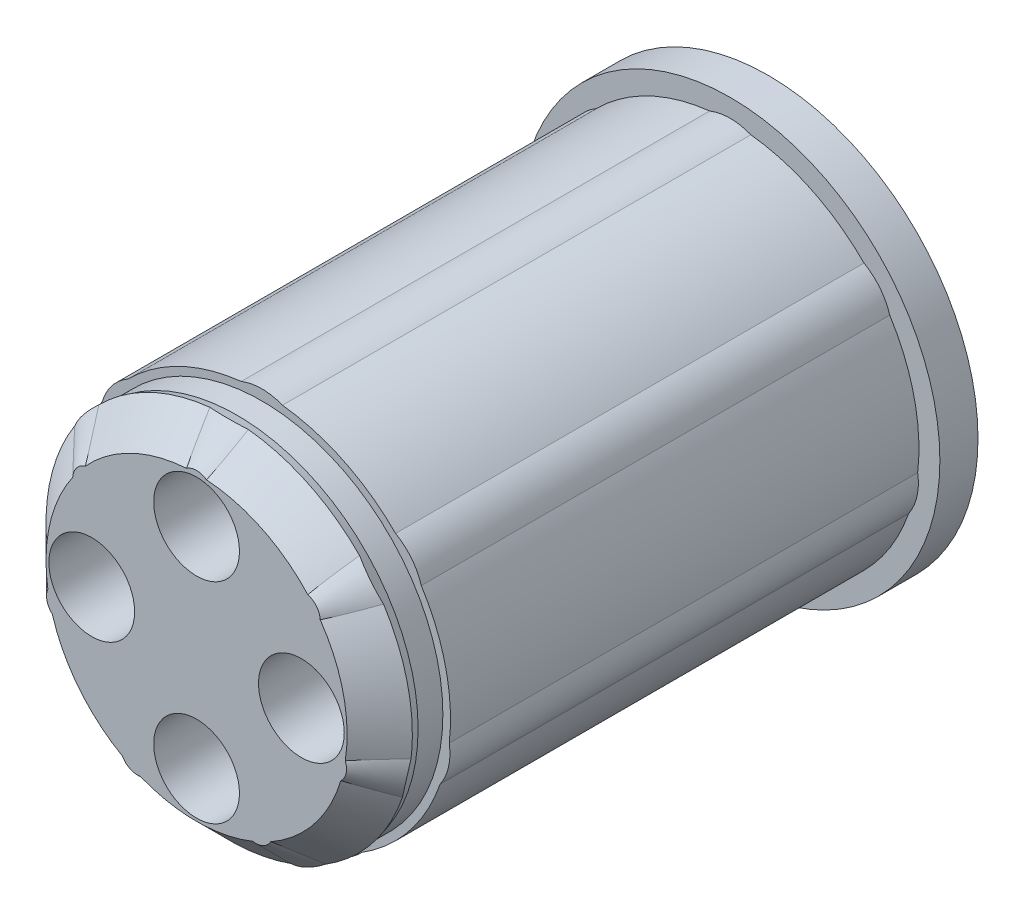
SolidWorks part; units mm, degrees
ref_plane "Ebene vorne" through (0, 0, 0) normal (0, 0, 1) x (1, 0, 0)
ref_plane "Ebene oben" through (0, 0, 0) normal (0, 1, 0) x (1, 0, 0)
ref_plane "Ebene rechts" through (0, 0, 0) normal (1, 0, 0) x (0, 0, -1)
sketch "Skizze1" plane through (0, 0, 0) normal (0, 0, 1) x (1, 0, 0)
  line L0 (0, 0) -> (0, 7.15) construction
  circle A0 centre (0, 0) radius 9.9
  circle A1 centre (0, 0) radius 10.05 construction
  circle A2 centre (0, 7.15) radius 2.9
  circle A7 centre (5.5901, 4.458) radius 2.9
  circle A8 centre (6.9707, -1.591) radius 2.9
  circle A9 centre (3.1023, -6.4419) radius 2.9
  circle A10 centre (-3.1023, -6.4419) radius 2.9
  circle A11 centre (-6.9707, -1.591) radius 2.9
  circle A12 centre (-5.5901, 4.458) radius 2.9
  point P17 (0, 0)
  point P21 (0, 0)
  dimension "D1" = 19.8
  dimension "D2" = 20.1
  dimension "D3" = 5.8
  dimension "D4" = 7
extrude "Aufsatz-Linear austragen1" add sketch "Skizze1" along normal blind 30 contours A0 A12 | A0 A2 | A0 A7 | A0 A8 | A0 A9 | A0 A10 | A0 A11 | A0 A11 | A0 A12 | A0 A2 | A0 A8 | A0 A9 | A0 A10 | A12 A0 A11 A10 A9 A8 A7 A2 | A0 A7 region at (0, 0, 0) region at (5.5718, 4.4434, 0) region at (7.7779, 6.2027, 0) region at (9.6989, -2.2137, 0) region at (6.948, -1.5858, 0) region at (0, 7.1267, 0) region at (0, 9.9483, 0) region at (4.3164, -8.9631, 0) region at (3.0921, -6.4209, 0) region at (-5.5718, 4.4434, 0) region at (-7.7779, 6.2027, 0) region at (-4.3164, -8.9631, 0) region at (-3.0921, -6.4209, 0) region at (-6.948, -1.5858, 0) region at (-9.6989, -2.2137, 0)
sketch "Skizze2" plane through (0, 0, 0) normal (0, 0, 1) x (1, 0, 0)
  circle A0 centre (0, 0) radius 11
  dimension "D1" = 22
extrude "Aufsatz-Linear austragen2" add sketch "Skizze2" along normal blind 2
chamfer "Fase1" distance 2 angle 45 14 edges at (9.798, -2.2363, 30) (7.7401, -6.1725, 30) (4.3605, -9.0547, 30) (0, -9.9, 30) (-4.3605, -9.0547, 30) (-7.7401, -6.1725, 30) (-9.798, -2.2363, 30) (-9.6518, 2.203, 30) (-7.8574, 6.2661, 30) (-4.2954, 8.9196, 30) (0, 10.05, 30) (4.2954, 8.9196, 30) (7.8574, 6.2661, 30) (9.6518, 2.203, 30)
sketch "Skizze3" plane through (0, 0, 2) normal (0, 0, 1) x (1, 0, 0)
  line L0 (0, 0) -> (0, 5.5) construction
  circle A0 centre (0, 0) radius 5.5 construction
  circle A1 centre (0, 5.5) radius 2.25
  circle A2 centre (5.5, 0) radius 2.25
  circle A3 centre (0, -5.5) radius 2.25
  circle A4 centre (-5.5, 0) radius 2.25
  point P14 (0, 0)
  dimension "D1" = 5.5
  dimension "D2" = 4.5
  dimension "D3" = 4
extrude "Schnitt-Linear austragen1" cut sketch "Skizze3" against normal through all and the other way through all
sketch "Skizze4" plane through (0, 0, 0) normal (1, 0, 0) x (0, 0, -1)
  line L0 (-2, 10.05) -> (-28, 10.05) construction
  line L1 (-27.8766, 10.05) -> (-26.5766, 10.05)
  line L2 (-27.8766, 10.05) -> (-27.8766, 9.5) construction
  line L3 (-27.8766, 9.5) -> (-26.5766, 9.5)
  line L4 (-26.5766, 10.05) -> (-26.5766, 9.5)
  line L5 (-27.8766, 9.5) -> (-29.9292, 10.05)
  line L6 (0, 0) -> (3.3435, 0) construction
  line L7 (-26.1766, 11.225) -> (-26.1766, -11.225) construction
  line L10 (-29.9292, 10.05) -> (-27.8766, 10.05)
  dimension "D1" = 0.4
  dimension "D2" = 19
  dimension "D3" = 1.3
  dimension "D4" = 75
revolve "Schnitt-Rotation1" cut sketch "Skizze4" angle 360 about L6
ref_axis "Achse1" through (0, 0, -1.5) along (0, 0, 1)
